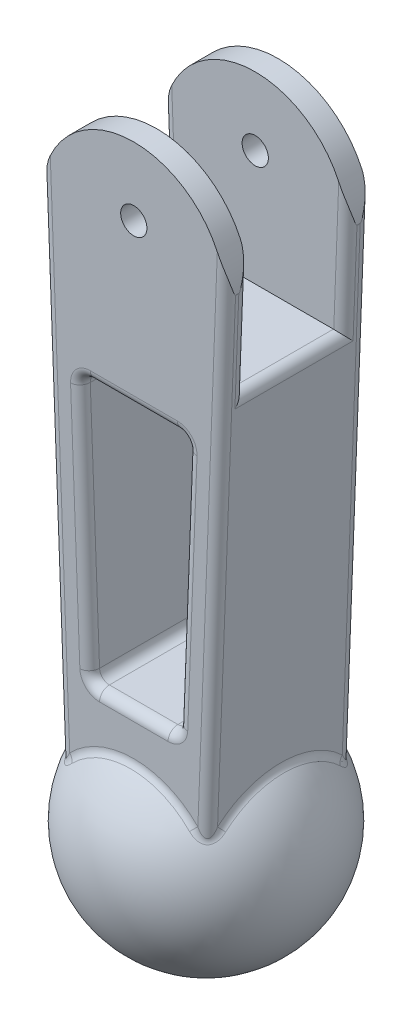
SolidWorks part; units mm, degrees
ref_plane "Front Plane" through (0, 0, 0) normal (0, 0, 1) x (1, 0, 0)
ref_plane "Top Plane" through (0, 0, 0) normal (0, 1, 0) x (1, 0, 0)
ref_plane "Right Plane" through (0, 0, 0) normal (1, 0, 0) x (0, 0, -1)
sketch "Sketch1" plane through (0, 0, 0) normal (0, 0, 1) x (1, 0, 0)
  line L0 (0, 21.59) -> (0, -21.59) construction
  line L1 (0, 21.59) -> (0, -21.59)
  arc A0 (0, -21.59) -> (0, 21.59) centre (0, 0) ccw
  dimension "D1" = 43.18
revolve "Revolve4" add sketch "Sketch1" angle 360 about L0
sketch "Sketch3" plane through (0, 0, 0) normal (0, 0, 1) x (1, 0, 0)
  line L0 (0, 0) -> (0, 102.87) construction
  line L3 (-13.843, 0) -> (13.843, 0)
  line L8 (13.843, 0) -> (17.78, 102.87)
  line L9 (-13.843, 0) -> (-17.78, 102.87)
  arc A0 (17.78, 102.87) -> (-17.78, 102.87) centre (0, 102.87) ccw
  point P6 (0, 102.87)
  point P11 (0, 102.87)
  dimension "D3" = 92.192
  dimension "D5" = 17.78
  dimension "D1" = 102.87
  dimension "D2" = 35.56
  dimension "D4" = 27.686
  dimension "D6" = 92.192
extrude "Boss-Extrude1" add sketch "Sketch3" along normal mid plane 27.94
sketch "Sketch4" plane through (0, 0, 13.97) normal (0, 0, 1) x (1, 0, 0)
  line L0 (0, 102.87) -> (0, 107.442)
  circle A0 centre (0, 107.442) radius 2.54
  dimension "D2" = 5.08
  dimension "D1" = 4.572
extrude "Cut-Extrude2" cut sketch "Sketch4" against normal through all
ref_plane "Plane1" through (0, 0, 0) normal (0, 0, 1) x (1, 0, 0)
sketch "Sketch6" plane through (0, 0, 0) normal (0, 0, 1) x (1, 0, 0)
  line L0 (-17.0995, 85.09) -> (17.0995, 85.09)
  line L1 (14.164, 8.3874) -> (17.78, 102.87) construction
  line L2 (-14.164, 8.3874) -> (-17.78, 102.87) construction
  line L3 (-17.78, 102.87) -> (17.78, 102.87) construction
  line L4 (-17.78, 102.87) -> (-17.0995, 85.09)
  line L5 (17.78, 102.87) -> (17.0995, 85.09)
  arc A2 (17.78, 102.87) -> (-17.78, 102.87) centre (0, 102.87) ccw
  point P5 (0, 102.87)
  point P11 (0, 85.09)
  dimension "D1" = 17.78
extrude "Cut-Extrude4" cut sketch "Sketch6" against normal mid plane 19.05 contours L5 L0 L4 A2
sketch "Sketch7" plane through (0, 0, 13.97) normal (0, 0, 1) x (1, 0, 0)
  line L7 (-7.8186, 8.6302) -> (-11.4346, 103.1128)
  line L8 (-8.4604, 25.4) -> (-10.4046, 76.2)
  line L9 (-8.4604, 25.4) -> (8.4604, 25.4)
  line L10 (7.8186, 8.6302) -> (11.4346, 103.1128)
  line L11 (8.4604, 25.4) -> (10.4046, 76.2)
  line L12 (-10.4046, 76.2) -> (10.4046, 76.2)
  dimension "D3" = 25.4
  dimension "D4" = 50.8
  dimension "D1" = 6.35
  dimension "D2" = 6.35
extrude "Cut-Extrude5" cut sketch "Sketch7" against normal through all
fillet "Fillet1" radius 1.905 30 edges at (0, 25.4, -13.97) (0, 76.2, -13.97) (0, 76.2, 13.97) (0, 25.4, 13.97) (-17.4398, 93.98, 9.525) (-17.78, 102.87, 11.7475) (-15.972, 55.6287, 13.97) (-15.972, 55.6287, -13.97) (-17.78, 102.87, -11.7475) (-17.4398, 93.98, -9.525) (-17.0995, 85.09, 0) (9.4325, 50.8, -13.97) (10.4046, 76.2, 0) (9.4325, 50.8, 13.97) (8.4604, 25.4, 0) (17.0995, 85.09, 0) (-9.4325, 50.8, -13.97) (-8.4604, 25.4, 0) (-9.4325, 50.8, 13.97) (-10.4046, 76.2, 0) (17.78, 102.87, -11.7475) (15.972, 55.6287, -13.97) (15.972, 55.6287, 13.97) (17.78, 102.87, 11.7475) (17.4398, 93.98, 9.525) (17.4398, 93.98, -9.525) (0, 16.4611, 13.97) (0, 16.4611, -13.97) (14.4567, 16.0353, 0) (-14.4567, 16.0353, 0)
